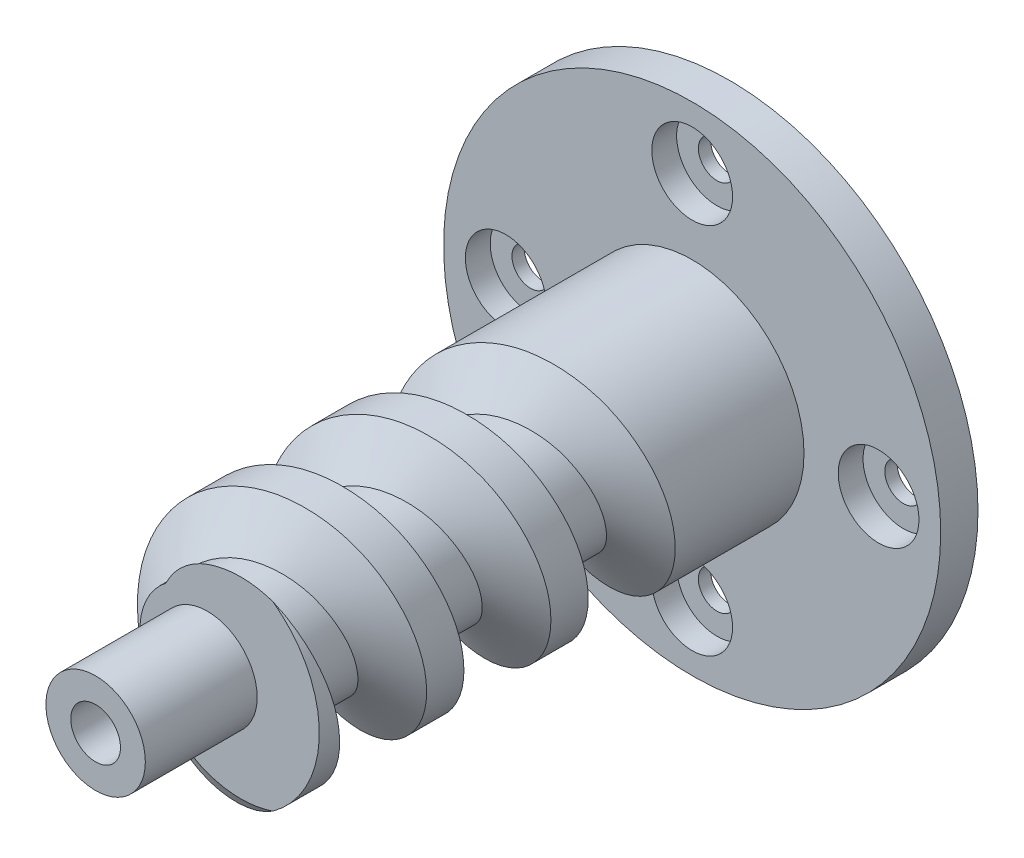
SolidWorks part; units mm, degrees
ref_plane "Front Plane" through (0, 0, 0) normal (0, 0, 1) x (1, 0, 0)
ref_plane "Top Plane" through (0, 0, 0) normal (0, 1, 0) x (1, 0, 0)
ref_plane "Right Plane" through (0, 0, 0) normal (1, 0, 0) x (0, 0, -1)
sketch "Sketch1" plane through (0, 0, 0) normal (0, 0, 1) x (1, 0, 0)
  circle A0 centre (0, 0) radius 20
  dimension "D1" = 40
extrude "Extrude1" add sketch "Sketch1" along normal blind 3
sketch "Sketch2" plane through (0, 0, 3) normal (0, 0, 1) x (1, 0, 0)
  circle A0 centre (0, 0) radius 9
  dimension "D1" = 18
extrude "Extrude2" add sketch "Sketch2" along normal blind 6
sketch "Sketch3" plane through (0, 0, 9) normal (0, 0, 1) x (1, 0, 0)
  circle A0 centre (0, 0) radius 9
  dimension "D1" = 18
extrude "Extrude3" add sketch "Sketch3" along normal blind 33
sketch "Sketch4" plane through (0, 0, 42) normal (0, 0, 1) x (1, 0, 0)
  circle A0 centre (0, 0) radius 9
  circle A1 centre (0, 0) radius 9 construction
curve "Helix/Spiral1" pitch 10 height 30 turns 3
sketch "Sketch5" plane through (0, 0, 0) normal (0, 1, 0) x (1, 0, 0)
  line L0 (-5.4378, -40.5566) -> (-5.4378, -43.4434)
  line L1 (-2.9378, -42) -> (-12.0311, -36.75) construction
  line L2 (-12.0311, -36.75) -> (-12.0311, -47.25)
  line L3 (-12.0311, -47.25) -> (-2.9378, -42) construction
  line L4 (-5.4378, -40.5566) -> (-12.0311, -36.75)
  line L5 (-5.4378, -43.4434) -> (-12.0311, -47.25)
  circle A0 centre (-9, -42) radius 6.0622 construction
  dimension "D1" = 10.5
  dimension "D2" = 2.5
sweep "Cut-Sweep1" cut profiles "Sketch5" path "Helix/Spiral1"
sketch "Sketch6" plane through (0, 0, 42) normal (0, 0, 1) x (1, 0, 0)
  circle A0 centre (0, 0) radius 4
  dimension "D1" = 8
extrude "Extrude4" add sketch "Sketch6" along normal blind 9
hole_wizard "CBORE for M3 Pan Head Machine Screw1" positions "3DSketch1" profile "Sketch7" counterbore size "M3" standard "Ansi Metric" end condition through all
sketch3d "3DSketch1"
  line L2 (0, 15, 3) -> (0, -15, 3) construction
  line L8 (-15, 0, 3) -> (15, 0, 3) construction
  point P0 (15, 0, 3)
  point P2 (0, -15, 3)
  point P4 (-15, 0, 3)
  point P6 (0, 15, 3)
  point P18 (0, 0, 3)
  point P33 (0, 0, 3)
  dimension "D1" = 30
  dimension "D2" = 30
sketch "Sketch7" plane through (15, 0, 3) normal (1, 0, 0) x (0, -1, 0)
  line L0 (0, 0) -> (0, 3)
  line L1 (0, 3) -> (1.5, 3)
  line L3 (1.5, 3) -> (1.5, 2)
  line L4 (1.5, 2) -> (3.25, 2)
  line L5 (3.25, 2) -> (3.25, 0)
  line L7 (3.25, 0) -> (0, 0)
  line L11 (0, -6.35) -> (0, 107.95) construction
  dimension "Thru Hole Dia." = 3
  dimension "Thru Hole Depth" = 3
  dimension "C'Bore Dia." = 6.5
  dimension "C'Bore Depth" = 2
sketch "Sketch8" plane through (0, 0, 0) normal (0, 0, -1) x (-1, 0, 0)
  circle A0 centre (0, 0) radius 2
  dimension "D1" = 4
extrude "Extrude5" cut sketch "Sketch8" against normal through all
sketch "Sketch9" plane through (0, 0, 0) normal (0, 0, -1) x (-1, 0, 0)
  circle A0 centre (0, 0) radius 3.25
  dimension "D1" = 6.5
extrude "Extrude6" cut sketch "Sketch9" against normal blind 3
